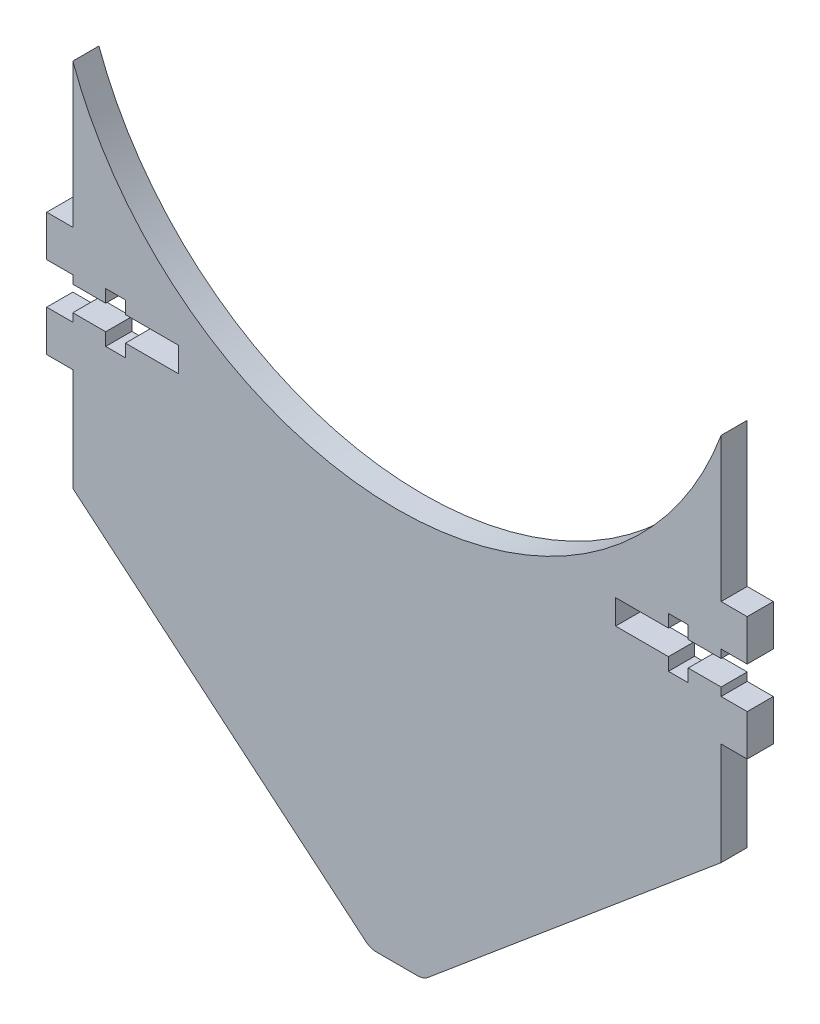
SolidWorks part; units mm, degrees
ref_plane "前视基准面" through (0, 0, 0) normal (0, 0, 1) x (1, 0, 0)
ref_plane "上视基准面" through (0, 0, 0) normal (0, 1, 0) x (1, 0, 0)
ref_plane "右视基准面" through (0, 0, 0) normal (1, 0, 0) x (0, 0, -1)
sketch "Sketch1" plane through (0, 0, 0) normal (0, 0, 1) x (1, 0, 0)
  line L0 (0, -85.8717) -> (0, 49.7374) construction
  line L2 (39.415, -20) -> (39.415, 25)
  line L4 (-39.415, -20) -> (-39.415, 25)
  line L6 (-3.7856, -49.8966) -> (-39.415, -20)
  line L8 (3.7856, -49.8966) -> (39.415, -20)
  line L9 (-39.415, 25) -> (39.415, 25) construction
  line L10 (2.5, -50.3645) -> (-2.5, -50.3645)
  arc A0 (39.415, 25) -> (-39.415, 25) centre (0, 39.5072) cw
  arc A3 (-3.7856, -49.8966) -> (-2.5, -50.3645) centre (-2.5, -48.3645) ccw
  arc A4 (3.7856, -49.8966) -> (2.5, -50.3645) centre (2.5, -48.3645) cw
  point P17 (0, -50.3645)
  dimension "D2" = 5
  dimension "D6" = 42
  dimension "D7" = 2
  dimension "D1" = 78.83
  dimension "D3" = 130
  dimension "D4" = 45
  dimension "D5" = 20
extrude "Boss-Extrude1" add sketch "Sketch1" along normal blind 3.175
sketch "Sketch2" plane through (0, 0, 3.175) normal (0, 0, 1) x (1, 0, 0)
  line L0 (-41.5791, 0) -> (41.497, 0) construction
  line L1 (0, 0) -> (0, 24.816) construction
  line L2 (39.415, -2.5) -> (39.415, -7.5)
  line L3 (39.415, -20) -> (39.415, 25) construction
  line L4 (39.415, -7.5) -> (42.59, -7.5)
  line L5 (42.59, -7.5) -> (42.59, -2.5)
  line L6 (42.59, -2.5) -> (39.415, -2.5)
  line L7 (39.415, -5) -> (51.6041, -5) construction
  line L8 (42.59, 2.5) -> (39.415, 2.5)
  line L9 (42.59, 7.5) -> (42.59, 2.5)
  line L10 (39.415, 7.5) -> (42.59, 7.5)
  line L11 (39.415, 2.5) -> (39.415, 7.5)
  line L12 (-39.415, -5) -> (-51.6041, -5) construction
  line L13 (-39.415, 2.5) -> (-39.415, 7.5)
  line L14 (-39.415, 7.5) -> (-42.59, 7.5)
  line L15 (-42.59, 7.5) -> (-42.59, 2.5)
  line L16 (-42.59, 2.5) -> (-39.415, 2.5)
  line L17 (-42.59, -2.5) -> (-39.415, -2.5)
  line L18 (-42.59, -7.5) -> (-42.59, -2.5)
  line L19 (-39.415, -7.5) -> (-42.59, -7.5)
  line L20 (-39.415, -2.5) -> (-39.415, -7.5)
  dimension "D1" = 5
  dimension "D2" = 3.175
  dimension "D3" = 5
extrude "Boss-Extrude2" add sketch "Sketch2" against normal blind 3.175
sketch "Sketch3" plane through (0, 0, 3.175) normal (0, 0, 1) x (1, 0, 0)
  line L0 (-43.1526, 0) -> (45.3724, 0) construction
  line L1 (39.415, 1.5) -> (35.415, 1.5)
  line L2 (39.415, 7.5) -> (39.415, 25) construction
  line L3 (35.415, 1.5) -> (35.415, 3.05)
  line L4 (35.415, 3.05) -> (33.015, 3.05)
  line L5 (33.015, 3.05) -> (33.015, 1.5)
  line L6 (33.015, 1.5) -> (26.59, 1.5)
  line L7 (39.415, 1.5) -> (39.415, -1.5)
  line L8 (26.59, 1.5) -> (26.59, -1.5)
  line L9 (33.015, -1.5) -> (26.59, -1.5)
  line L10 (33.015, -3.05) -> (33.015, -1.5)
  line L11 (35.415, -3.05) -> (33.015, -3.05)
  line L12 (35.415, -1.5) -> (35.415, -3.05)
  line L13 (39.415, -1.5) -> (35.415, -1.5)
  line L14 (42.59, -7.5) -> (42.59, -2.5) construction
  line L15 (0, 0) -> (0, 9.8166) construction
  line L16 (-39.415, -1.5) -> (-35.415, -1.5)
  line L17 (-35.415, -1.5) -> (-35.415, -3.05)
  line L18 (-35.415, -3.05) -> (-33.015, -3.05)
  line L19 (-33.015, -3.05) -> (-33.015, -1.5)
  line L20 (-33.015, -1.5) -> (-26.59, -1.5)
  line L21 (-26.59, 1.5) -> (-26.59, -1.5)
  line L22 (-39.415, 1.5) -> (-39.415, -1.5)
  line L23 (-33.015, 1.5) -> (-26.59, 1.5)
  line L24 (-33.015, 3.05) -> (-33.015, 1.5)
  line L25 (-35.415, 3.05) -> (-33.015, 3.05)
  line L26 (-35.415, 1.5) -> (-35.415, 3.05)
  line L27 (-39.415, 1.5) -> (-35.415, 1.5)
  point P14 (26.59, 0)
  point P15 (39.415, 0)
  point P35 (-39.415, 0)
  point P36 (-26.59, 0)
  dimension "D1" = 6.1
  dimension "D2" = 3
  dimension "D3" = 2.4
  dimension "D4" = 16
  dimension "D5" = 4
extrude "Cut-Extrude1" cut sketch "Sketch3" against normal through all
